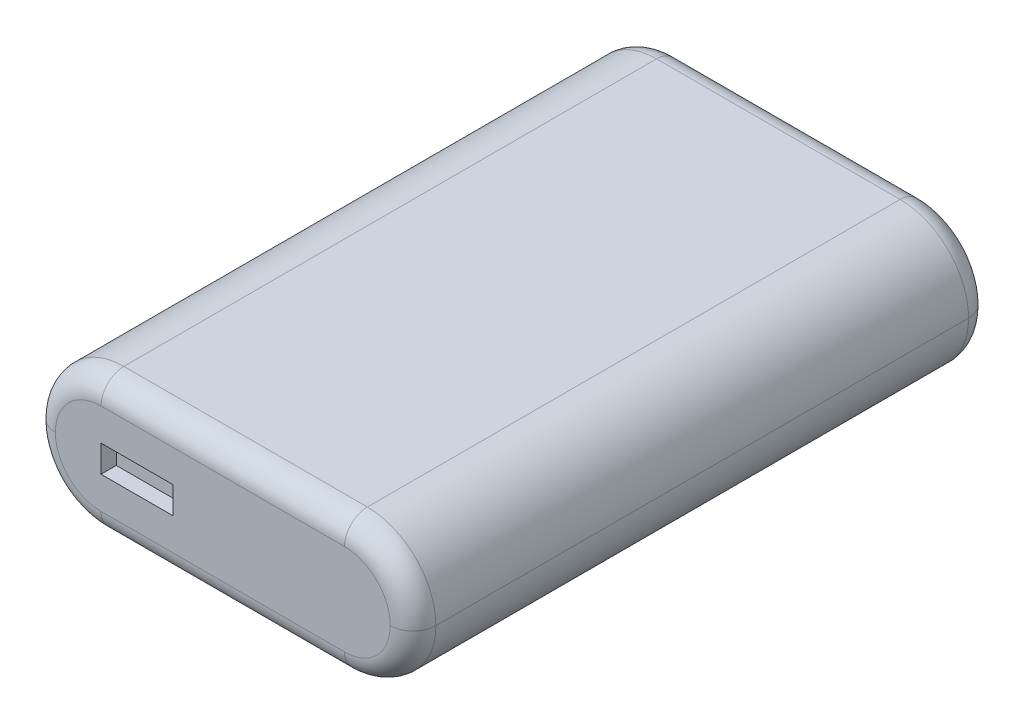
SolidWorks part; units mm, degrees
ref_plane "Front Plane" through (0, 0, 0) normal (0, 0, 1) x (1, 0, 0)
ref_plane "Top Plane" through (0, 0, 0) normal (0, 1, 0) x (1, 0, 0)
ref_plane "Right Plane" through (0, 0, 0) normal (1, 0, 0) x (0, 0, -1)
sketch "Sketch1" plane through (0, 0, 0) normal (0, 1, 0) x (1, 0, 0)
  line L1 (-31.75, 48.26) -> (31.75, 48.26)
  line L2 (-31.75, 48.26) -> (-31.75, -48.26)
  line L3 (-31.75, -48.26) -> (31.75, -48.26)
  line L4 (31.75, 48.26) -> (31.75, -48.26)
  line L5 (-31.75, 48.26) -> (31.75, -48.26) construction
  line L6 (-31.75, -48.26) -> (31.75, 48.26) construction
  point P0 (0, 0)
  dimension "D1" = 63.5
  dimension "D2" = 96.52
extrude "Boss-Extrude1" add sketch "Sketch1" along normal mid plane 22.86
fillet "Fillet1" radius 11.43 4 edges at (-31.75, -11.43, 0) (-31.75, 11.43, 0) (31.75, -11.43, 0) (31.75, 11.43, 0)
fillet "Fillet2" radius 3.81 12 edges at (-28.4022, 8.0822, 48.26) (-28.4022, -8.0822, 48.26) (0, -11.43, 48.26) (28.4022, -8.0822, 48.26) (28.4022, 8.0822, 48.26) (28.4022, 8.0822, -48.26) (28.4022, -8.0822, -48.26) (0, -11.43, -48.26) (-28.4022, -8.0822, -48.26) (-28.4022, 8.0822, -48.26) (0, 11.43, 48.26) (0, 11.43, -48.26)
sketch "Sketch2" plane through (0, 0, 48.26) normal (0, 0, 1) x (1, 0, 0)
  line L1 (-20.32, 2.25) -> (-8.32, 2.25)
  line L2 (-20.32, 2.25) -> (-20.32, -2.25)
  line L3 (-20.32, -2.25) -> (-8.32, -2.25)
  line L4 (-8.32, 2.25) -> (-8.32, -2.25)
  line L5 (-20.32, 2.25) -> (-8.32, -2.25) construction
  line L6 (-20.32, -2.25) -> (-8.32, 2.25) construction
  arc A3 (-20.32, 11.43) -> (-31.75, 0) centre (-20.32, 0) ccw construction
  point P0 (-14.32, 0)
  dimension "D1" = 4.5
  dimension "D2" = 12
  dimension "D3" = 11.43
extrude "Cut-Extrude1" cut sketch "Sketch2" against normal blind 2.54
